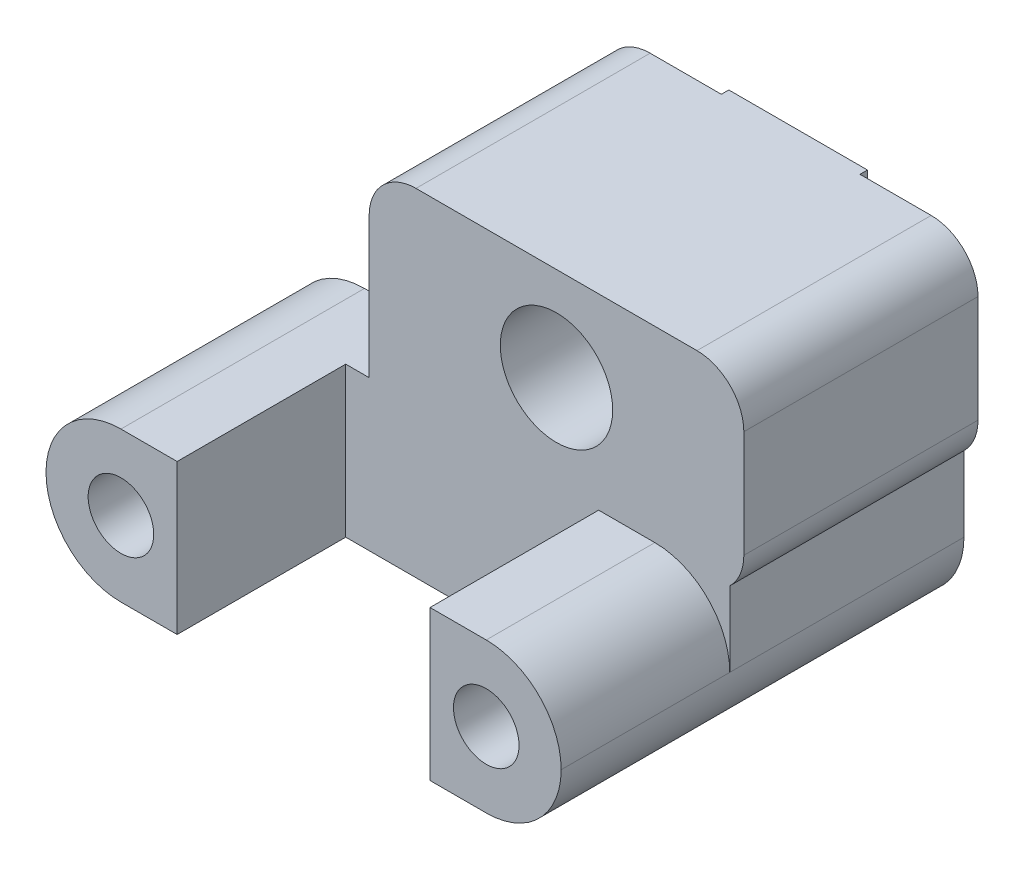
SolidWorks part; units mm, degrees
ref_plane "Спереди" through (0, 0, 0) normal (0, 0, 1) x (1, 0, 0)
ref_plane "Сверху" through (0, 0, 0) normal (0, 1, 0) x (1, 0, 0)
ref_plane "Справа" through (0, 0, 0) normal (1, 0, 0) x (0, 0, -1)
sketch "Эскиз1" plane through (0, 0, 0) normal (0, 0, 1) x (1, 0, 0)
  line L1 (0, 0) -> (20, 0)
  line L2 (0, 0) -> (0, -10)
  line L3 (0, -10) -> (20, -10)
  line L4 (20, 0) -> (20, -10)
  dimension "D1" = 10
  dimension "D2" = 20
extrude "Бобышка-Вытянуть1" add sketch "Эскиз1" along normal blind 8.5
sketch "Эскиз4" plane through (0, 0, 8.5) normal (0, 0, -1) x (-1, 0, 0)
  line L2 (0, -10) -> (-20, -10) construction
  line L3 (4.25, -14) -> (-15.25, -14) construction
  line L5 (4.25, -10) -> (0, -10)
  line L6 (0, -10) -> (0, 0)
  line L8 (0, 0) -> (0, -10) construction
  line L9 (0, 0) -> (-20, 0)
  line L13 (-20, 0) -> (-20, -10)
  line L14 (4.25, -18) -> (-15.25, -18)
  line L15 (-19.25, -14) -> (-19.25, -10)
  line L16 (-19.25, -10) -> (-20, -10)
  arc A0 (4.25, -18) -> (4.25, -10) centre (4.25, -14) ccw
  arc A1 (-19.25, -14) -> (-15.25, -18) centre (-15.25, -14) ccw
  point P3 (-5.5, -14)
  dimension "D1" = 8
  dimension "D2" = 8
  dimension "D3" = 19.5
  dimension "D4" = 5.5
  dimension "D5" = 4.25
extrude "Бобышка-Вытянуть3" add sketch "Эскиз4" against normal blind 13 and the other way up to surface (8.5 mm away) other way up to face at (10, -5, 0)
sketch "Эскиз5" plane through (0, 0, 21.5) normal (0, 0, 1) x (1, 0, 0)
  line L2 (-1.25, -10) -> (-1.25, -18)
  line L3 (-1.25, -18) -> (12.25, -18)
  line L4 (12.25, -10) -> (12.25, -18)
  line L16 (15.25, -18) -> (-4.25, -18) construction
  line L17 (-4.25, -10) -> (0, -10) construction
  line L18 (12.25, -10) -> (20, -10)
  line L19 (20, -10) -> (20, 0)
  line L20 (20, 0) -> (0, 0)
  line L21 (0, 0) -> (0, -10)
  line L22 (0, -10) -> (0, 0) construction
  line L23 (0, -10) -> (-1.25, -10)
  point P9 (5.5, -18)
  point P10 (5.5, -18)
  dimension "D1" = 13.5
extrude "Вырез-Вытянуть1" cut sketch "Эскиз5" against normal blind 9
sketch "Эскиз11" plane through (0, 0, 0) normal (0, 0, -1) x (-1, 0, 0)
  line L0 (4.25, -18) -> (-15.25, -18) construction
  line L1 (-6.3, -18) -> (-13.7, -18)
  line L2 (-6.3, -18) -> (-6.3, 0)
  line L3 (-6.3, 0) -> (-13.7, 0)
  line L4 (-13.7, -18) -> (-13.7, 0)
  line L7 (-20, 0) -> (0, 0) construction
  line L8 (0, 0) -> (0, -10) construction
  point P8 (-10, 0)
  dimension "D1" = 18
  dimension "D2" = 7.4
  dimension "D3" = 10
extrude "Бобышка-Вытянуть5" add sketch "Эскиз11" along normal blind 0.4
sketch "Эскиз14" plane through (9.75, -18, 0) normal (0, 1, 0) x (-1, 0, 0)
  line L5 (13.25, 8.5) -> (26.25, 8.5)
  line L6 (13.25, 8.5) -> (13.25, 0)
  line L7 (13.25, 0) -> (26.25, 0)
  line L8 (26.25, 8.5) -> (26.25, 0)
  line L11 (-3.95, -0.4) -> (3.45, -0.4) construction
  line L14 (14, 0) -> (3.45, 0) construction
  point P12 (-0.25, -0.4)
  point P13 (19.75, 0)
  dimension "D1" = 13
  dimension "D2" = 8.5
  dimension "D3" = 20
extrude "Вырез-Вытянуть7" cut sketch "Эскиз14" against normal up to surface (-8 mm away) up to face at (19.625, -10, 6.25)
sketch "Эскиз6" plane through (0, 0, 21.5) normal (0, 0, 1) x (1, 0, 0)
  circle A0 centre (-4.25, -14) radius 1.75
  circle A1 centre (15.25, -14) radius 1.75
  dimension "D1" = 3.5
  dimension "D2" = 3.5
extrude "Вырез-Вытянуть2" cut sketch "Эскиз6" against normal offset from surface (12.8 mm away) 0.2 up to face at (-4.875, -14, 8.5)
sketch "Эскиз7" plane through (0, 0, 0) normal (0, 0, -1) x (-1, 0, 0)
  line L1 (-15.25, -10.7668) -> (-18.05, -12.3834)
  line L2 (-18.05, -12.3834) -> (-18.05, -15.6166)
  line L3 (-18.05, -15.6166) -> (-15.25, -17.2332)
  line L4 (-15.25, -17.2332) -> (-12.45, -15.6166)
  line L5 (-12.45, -15.6166) -> (-12.45, -12.3834)
  line L6 (-12.45, -12.3834) -> (-15.25, -10.7668)
  line L7 (4.25, -10.7668) -> (1.45, -12.3834)
  line L8 (1.45, -12.3834) -> (1.45, -15.6166)
  line L9 (1.45, -15.6166) -> (4.25, -17.2332)
  line L10 (4.25, -17.2332) -> (7.05, -15.6166)
  line L11 (7.05, -15.6166) -> (7.05, -12.3834)
  line L12 (7.05, -12.3834) -> (4.25, -10.7668)
  circle A0 centre (-15.25, -14) radius 2.8 construction
  circle A1 centre (4.25, -14) radius 2.8 construction
  dimension "D1" = 5.6
  dimension "D2" = 5.6
extrude "Вырез-Вытянуть3" cut sketch "Эскиз7" against normal offset from surface 8.6 and the other way through all up to face at (-2.5, -14, 21.5)
sketch "Эскиз15" plane through (0, 0, 0) normal (0, 0, -1) x (-1, 0, 0)
  line L0 (0, -10) -> (0, -18)
  line L1 (0, -10) -> (3.5, -10) construction
  line L2 (3.5, -18) -> (-6.3, -18) construction
  line L3 (0, -18) -> (3.5, -18)
  line L4 (3.5, -18) -> (3.5, -10)
  line L5 (3.5, -10) -> (0, -10)
  line L6 (0, 0) -> (0, -10) construction
extrude "Вырез-Вытянуть8" cut sketch "Эскиз15" against normal up to surface (8.5 mm away) up to face at (-4.91, -14, 8.5)
sketch "Эскиз12" plane through (0, 0, -0.4) normal (0, 0, -1) x (-1, 0, 0)
  line L0 (-6.3, 0) -> (-13.7, 0) construction
  line L1 (0, 0) -> (0, -18) construction
  circle A0 centre (-10, -5) radius 1.6
  dimension "D1" = 3.2
  dimension "D2" = 5
  dimension "D3" = 10
extrude "Вырез-Вытянуть4" cut sketch "Эскиз12" against normal through all
sketch "Эскиз13" plane through (0, 0, 12.5) normal (0, 0, 1) x (1, 0, 0)
  circle A0 centre (10, -5) radius 3
  dimension "D1" = 6
extrude "Вырез-Вытянуть5" cut sketch "Эскиз13" against normal offset from surface (4.5 mm away) 8 up to face at (3.15, -9, 0)
fillet "Скругление1" radius 2.5 3 edges at (0, 0, 6.25) (20, 0, 6.25) (20, -10, 6.25)
fillet "Скругление2" radius 4 1 edges at (19.25, -10, 17)
